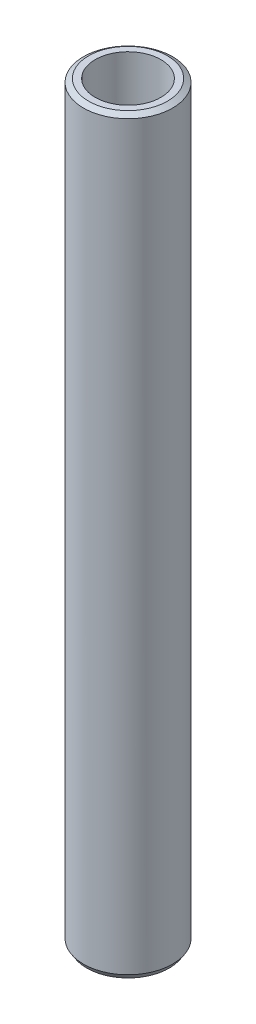
SolidWorks part; units mm, degrees
ref_plane "Front Plane" through (0, 0, 0) normal (0, 0, 1) x (1, 0, 0)
ref_plane "Top Plane" through (0, 0, 0) normal (0, 1, 0) x (1, 0, 0)
ref_plane "Right Plane" through (0, 0, 0) normal (1, 0, 0) x (0, 0, -1)
sketch "Sketch1" plane through (0, 0, 0) normal (0, 1, 0) x (1, 0, 0)
  circle A0 centre (0, 0) radius 20
  dimension "SHAFT_OD" = 40
extrude "Boss-Extrude1" add sketch "Sketch1" along normal blind 336.4985
sketch "Sketch2" plane through (0, 0, 0) normal (0, 1, 0) x (1, 0, 0)
  circle A0 centre (0, 0) radius 14.7234
  dimension "BORE_D" = 29.4468
extrude "Cut-Extrude1" cut sketch "Sketch2" along normal through all
chamfer "Chamfer1" distance 1.5016 angle 57.19 2 edges at (0, 336.4985, 20) (0, 0, 20) first distance on face at (0, 336.4985, 20) first distance on face at (0, 0, 14.7234)
